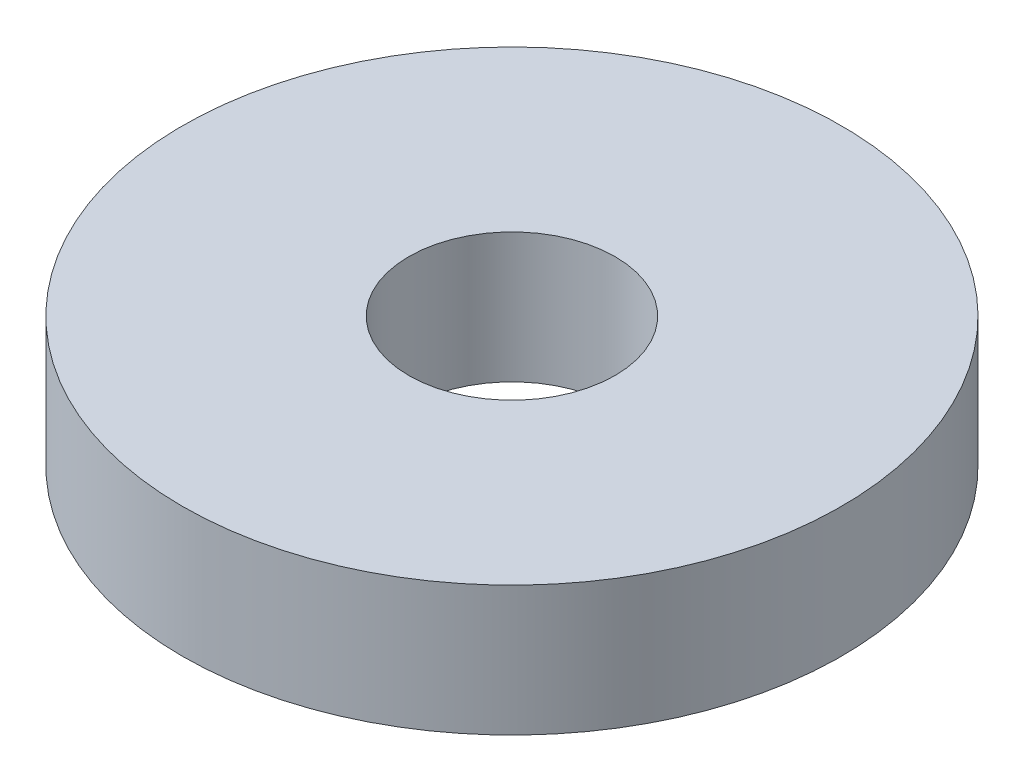
SolidWorks part; units mm, degrees
material "AISI 1020 Steel, Cold Rolled"
ref_plane "Front Plane" through (0, 0, 0) normal (0, 0, 1) x (1, 0, 0)
ref_plane "Top Plane" through (0, 0, 0) normal (0, 1, 0) x (1, 0, 0)
ref_plane "Right Plane" through (0, 0, 0) normal (1, 0, 0) x (0, 0, -1)
sketch "Sketch1" plane through (0, 0, 0) normal (0, 1, 0) x (1, 0, 0)
  circle A0 centre (0, 0) radius 2.3813
  circle A1 centre (0, 0) radius 7.6136
  circle A2 centre (0, 0) radius 7.6136 construction
  dimension "D1" = 4.7625
extrude "Boss-Extrude1" add sketch "Sketch1" along normal blind 3
